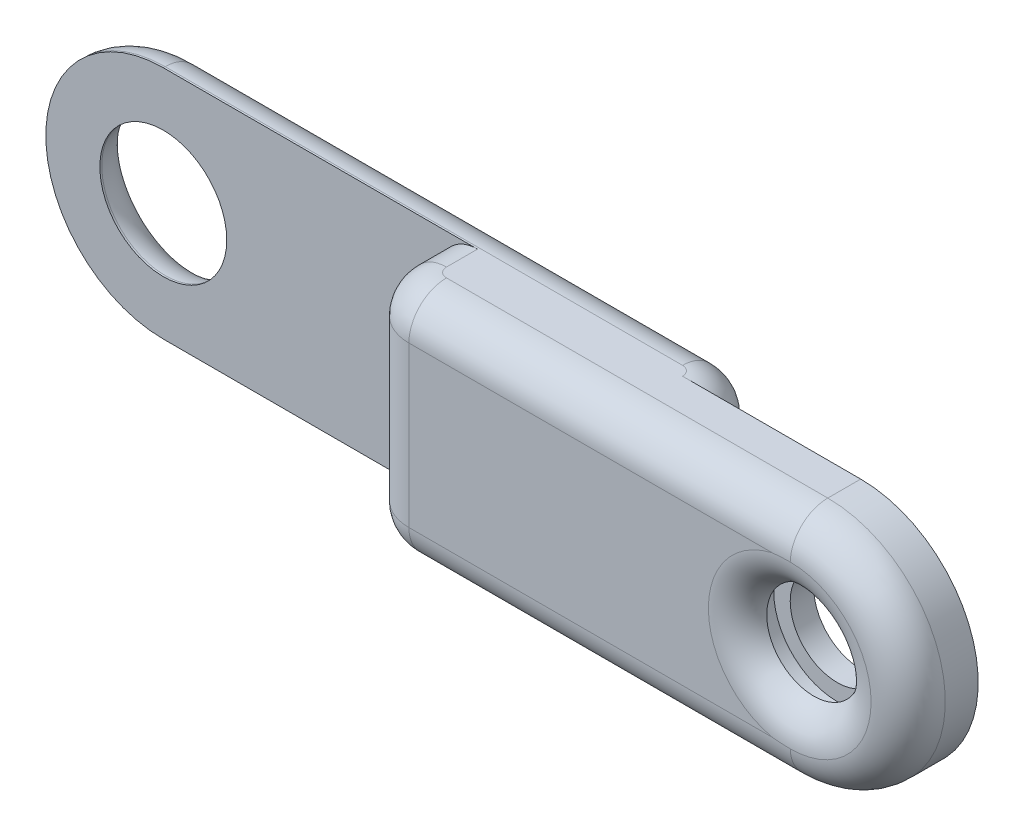
SolidWorks part; units mm, degrees
ref_plane "Front Plane" through (0, 0, 0) normal (0, 0, 1) x (1, 0, 0)
ref_plane "Top Plane" through (0, 0, 0) normal (0, 1, 0) x (1, 0, 0)
ref_plane "Right Plane" through (0, 0, 0) normal (1, 0, 0) x (0, 0, -1)
sketch "Sketch1" plane through (0, 0, 0) normal (0, 0, 1) x (1, 0, 0)
  line L0 (-154.9449, 0) -> (-4.9449, 0) construction
  line L1 (-154.9449, 25) -> (-4.9449, 25)
  line L2 (-154.9449, -25) -> (-4.9449, -25)
  arc A0 (-154.9449, 25) -> (-154.9449, -25) centre (-154.9449, 0) ccw
  arc A1 (-4.9449, -25) -> (-4.9449, 25) centre (-4.9449, 0) ccw
  point P3 (-79.9449, 0)
  point P8 (-179.9449, 0)
  point P9 (20.0551, 0)
  dimension "D2" = 25
  dimension "D1" = 200
extrude "Boss-Extrude1" add sketch "Sketch1" along normal blind 25
sketch "Sketch2" plane through (0, 0, 25) normal (0, 0, 1) x (1, 0, 0)
  circle A0 centre (-4.9449, 0) radius 13.5
  dimension "D1" = 27
extrude "Cut-Extrude1" cut sketch "Sketch2" against normal blind 25
sketch "Sketch3" plane through (0, 0, 25) normal (0, 0, 1) x (1, 0, 0)
  circle A0 centre (-154.9449, 0) radius 13.5
  dimension "D1" = 27
extrude "Cut-Extrude2" cut sketch "Sketch3" against normal blind 25
sketch "Sketch4" plane through (0, 0, 25) normal (0, 0, 1) x (1, 0, 0)
  circle A0 centre (-4.9449, 0) radius 13.5
  circle A1 centre (-4.9449, 0) radius 10
  dimension "D1" = 20
extrude "Boss-Extrude2" add sketch "Sketch4" against normal blind 5
sketch "Sketch5" plane through (0, 0, 0) normal (0, 0, -1) x (-1, 0, 0)
  circle A0 centre (4.9449, 0) radius 13.5
  circle A1 centre (4.9449, 0) radius 10
extrude "Boss-Extrude3" add sketch "Sketch5" against normal blind 15
sketch "Sketch6" plane through (0, 0, 0) normal (0, 0, -1) x (-1, 0, 0)
  line L0 (4.9449, 25) -> (34.8506, 25)
  line L1 (4.9449, 25) -> (154.9449, 25) construction
  line L2 (4.9449, -25) -> (34.8506, -25)
  line L3 (154.9449, -25) -> (4.9449, -25) construction
  line L4 (34.8506, -25) -> (34.8506, 25)
  arc A0 (4.9449, 25) -> (4.9449, -25) centre (4.9449, 0) ccw
extrude "Cut-Extrude3" cut sketch "Sketch6" against normal blind 10
sketch "Sketch7" plane through (0, 0, 25) normal (0, 0, 1) x (1, 0, 0)
  circle A0 centre (-154.9449, 0) radius 13.4686
extrude "Boss-Extrude4" add sketch "Sketch7" against normal blind 3 separate body
sketch "Sketch9" plane through (0, 0, 25) normal (0, 0, 1) x (1, 0, 0)
  line L0 (-96.0848, 25) -> (-96.0848, -25)
  line L1 (-4.9449, 25) -> (-154.9449, 25) construction
  line L2 (-154.9449, -25) -> (-4.9449, -25) construction
  line L3 (-96.0848, -25) -> (-154.9449, -25)
  line L5 (-154.9449, 25) -> (-96.0848, 25)
  arc A0 (-154.9449, 25) -> (-154.9449, -25) centre (-154.9449, 0) ccw
extrude "Cut-Extrude4" cut sketch "Sketch9" against normal blind 16.6
fillet "Fillet1" radius 10 1 edges at (-96.0848, 0, 25)
fillet "Fillet2" radius 10 1 edges at (-34.8506, 0, 0)
fillet "Fillet4" radius 8 14 edges at (-96.0848, -25, 11.7) (-93.1559, -25, 22.0711) (-96.0848, 25, 11.7) (-93.1559, 25, 22.0711) (-37.7795, 25, 2.9289) (-37.7795, -25, 2.9289) (5.0551, 0, 25) (20.0551, 0, 25) (-45.5148, -25, 25) (-45.5148, 25, 25) (-179.9449, 0, 0) (-99.8977, -25, 0) (-99.8977, 25, 0) (-141.4449, 0, 0)
